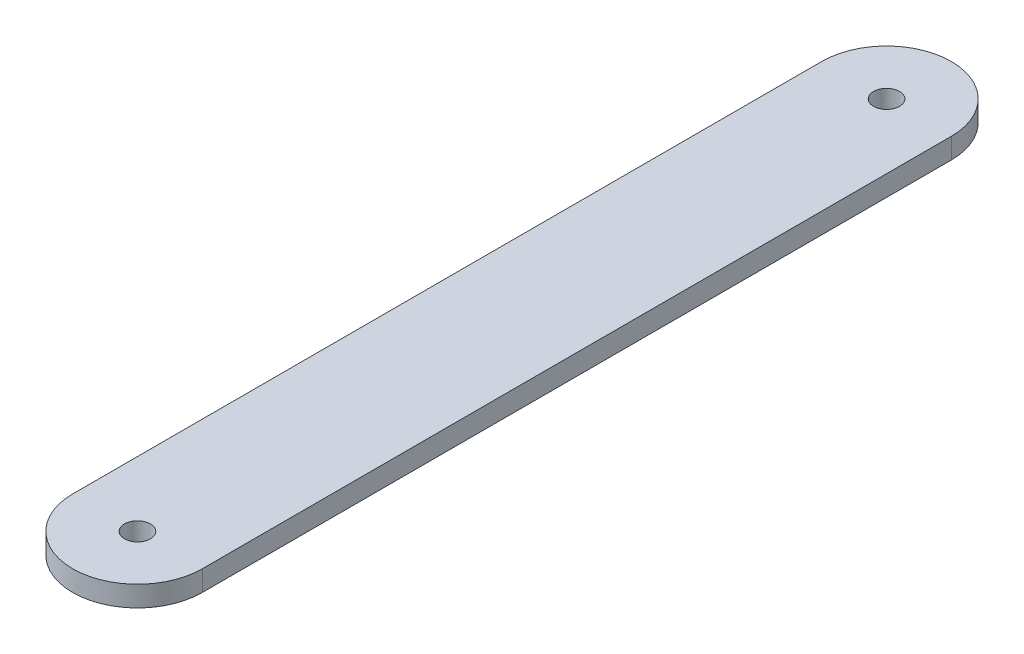
SolidWorks part; units mm, degrees
ref_plane "Front Plane" through (0, 0, 0) normal (0, 0, 1) x (1, 0, 0)
ref_plane "Top Plane" through (0, 0, 0) normal (0, 1, 0) x (1, 0, 0)
ref_plane "Right Plane" through (0, 0, 0) normal (1, 0, 0) x (0, 0, -1)
sketch "Sketch2" plane through (0, 0, 0) normal (0, 1, 0) x (1, 0, 0)
  line L0 (-5, 57.8) -> (-5, 0)
  line L1 (5, 57.8) -> (5, 0)
  circle A0 centre (0, 0) radius 1
  circle A1 centre (0, 57.8) radius 1
  arc A2 (5, 0) -> (-5, 0) centre (0, 0) cw
  arc A3 (5, 57.8) -> (-5, 57.8) centre (0, 57.8) ccw
  dimension "D2" = 2
  dimension "D3" = 5
  dimension "D1" = 57.8
extrude "Boss-Extrude1" add sketch "Sketch2" along normal blind 1.5875
